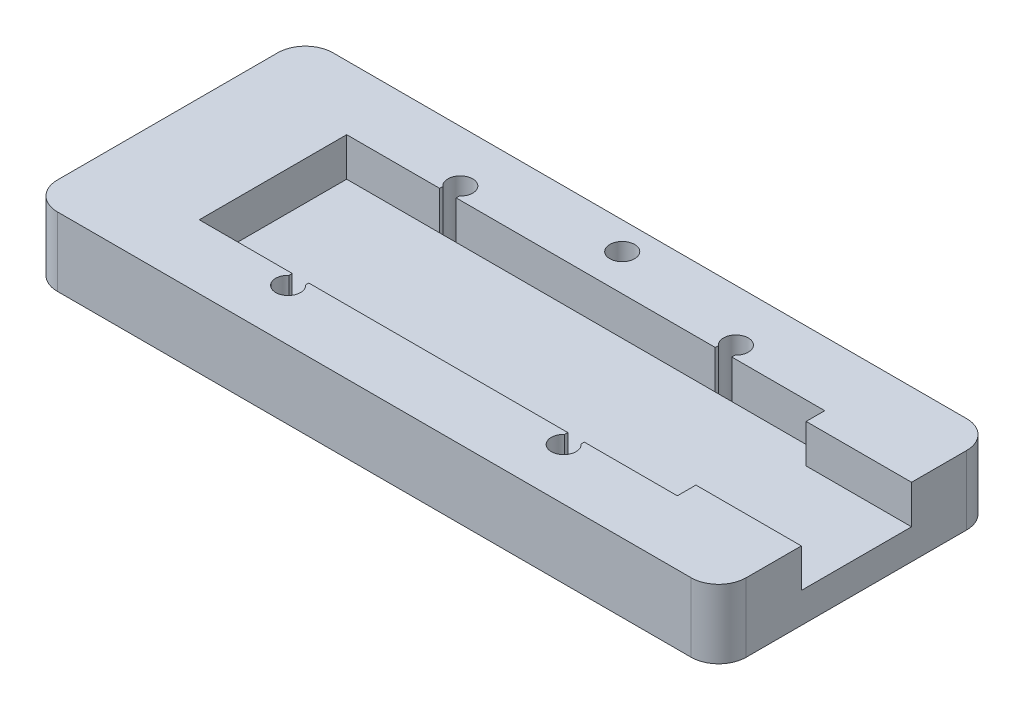
SolidWorks part; units mm, degrees
ref_plane "前基準面" through (0, 0, 0) normal (0, 0, 1) x (1, 0, 0)
ref_plane "上基準面" through (0, 0, 0) normal (0, 1, 0) x (1, 0, 0)
ref_plane "右基準面" through (0, 0, 0) normal (1, 0, 0) x (0, 0, -1)
sketch "草圖1" plane through (0, 0, 0) normal (0, 1, 0) x (1, 0, 0)
  line L1 (-23, -10) -> (23, -10)
  line L2 (-25, -8) -> (-25, 8)
  line L3 (-23, 10) -> (23, 10)
  line L4 (25, -8) -> (25, 8)
  line L5 (-25, -10) -> (25, 10) construction
  line L6 (-25, 10) -> (25, -10) construction
  arc A0 (23, 10) -> (25, 8) centre (23, 8) cw
  arc A1 (25, -8) -> (23, -10) centre (23, -8) cw
  arc A2 (-23, -10) -> (-25, -8) centre (-23, -8) cw
  arc A3 (-25, 8) -> (-23, 10) centre (-23, 8) cw
  point P0 (0, 0)
  dimension "D3" = 2
  dimension "D1" = 20
  dimension "D2" = 50
extrude "填料-伸長1" add sketch "草圖1" along normal blind 5
sketch "草圖2" plane through (0, 5, 0) normal (0, 1, 0) x (1, 0, 0)
  line L0 (25, -8) -> (25, 8) construction
  line L1 (-17.35, -5.35) -> (17.35, -5.35)
  line L2 (-17.35, -5.35) -> (-17.35, 5.35)
  line L3 (-17.35, 5.35) -> (17.35, 5.35)
  line L4 (17.35, -5.35) -> (17.35, -4)
  line L5 (-17.35, -5.35) -> (17.35, 5.35) construction
  line L6 (-17.35, 5.35) -> (17.35, -5.35) construction
  line L7 (17.35, -4) -> (25, -4)
  line L8 (0, 0) -> (-34.7994, 0) construction
  line L9 (17.35, 4) -> (25, 4)
  line L10 (25, -4) -> (25, 4)
  line L11 (17.35, 4) -> (17.35, 5.35)
  point P0 (0, 0)
  dimension "D1" = 34.7
  dimension "D2" = 10.7
  dimension "D3" = 8
extrude "除料-伸長1" cut sketch "草圖2" against normal blind 2.8
sketch "草圖3" plane through (0, 5, 0) normal (0, 1, 0) x (1, 0, 0)
  line L0 (0, 0) -> (0, 12.8997) construction
  line L1 (23, 10) -> (-23, 10) construction
  line L3 (17.35, 5.35) -> (-17.35, 5.35) construction
  line L4 (-10.6, 5.5792) -> (-10.6, 5.35)
  line L5 (-9.4, 5.5792) -> (-9.4, 5.35)
  line L6 (-10, 6.25) -> (-10, 2.7192) construction
  line L7 (-10.6, 5.35) -> (-9.4, 5.35)
  line L9 (0, 0) -> (-19.1874, 0) construction
  line L10 (-10.6, -5.35) -> (-9.4, -5.35)
  line L11 (-10.6, -5.5792) -> (-10.6, -5.35)
  line L12 (-9.4, -5.5792) -> (-9.4, -5.35)
  line L13 (10.6, 5.5792) -> (10.6, 5.35)
  line L14 (9.4, 5.5792) -> (9.4, 5.35)
  line L15 (9.4, -5.5792) -> (9.4, -5.35)
  line L16 (10.6, -5.5792) -> (10.6, -5.35)
  line L17 (10.6, -5.35) -> (9.4, -5.35)
  line L18 (9.4, 5.35) -> (10.6, 5.35)
  arc A0 (-9.4, 5.5792) -> (-10.6, 5.5792) centre (-10, 6.25) ccw
  arc A1 (-9.4, -5.5792) -> (-10.6, -5.5792) centre (-10, -6.25) cw
  arc A2 (9.4, 5.5792) -> (10.6, 5.5792) centre (10, 6.25) cw
  arc A3 (9.4, -5.5792) -> (10.6, -5.5792) centre (10, -6.25) ccw
  circle A4 centre (0, 8) radius 0.9
  dimension "D1" = 1.8
  dimension "D4" = 2
  dimension "D2" = 10
  dimension "D3" = 1.2
extrude "除料-伸長2" cut sketch "草圖3" against normal blind 5
